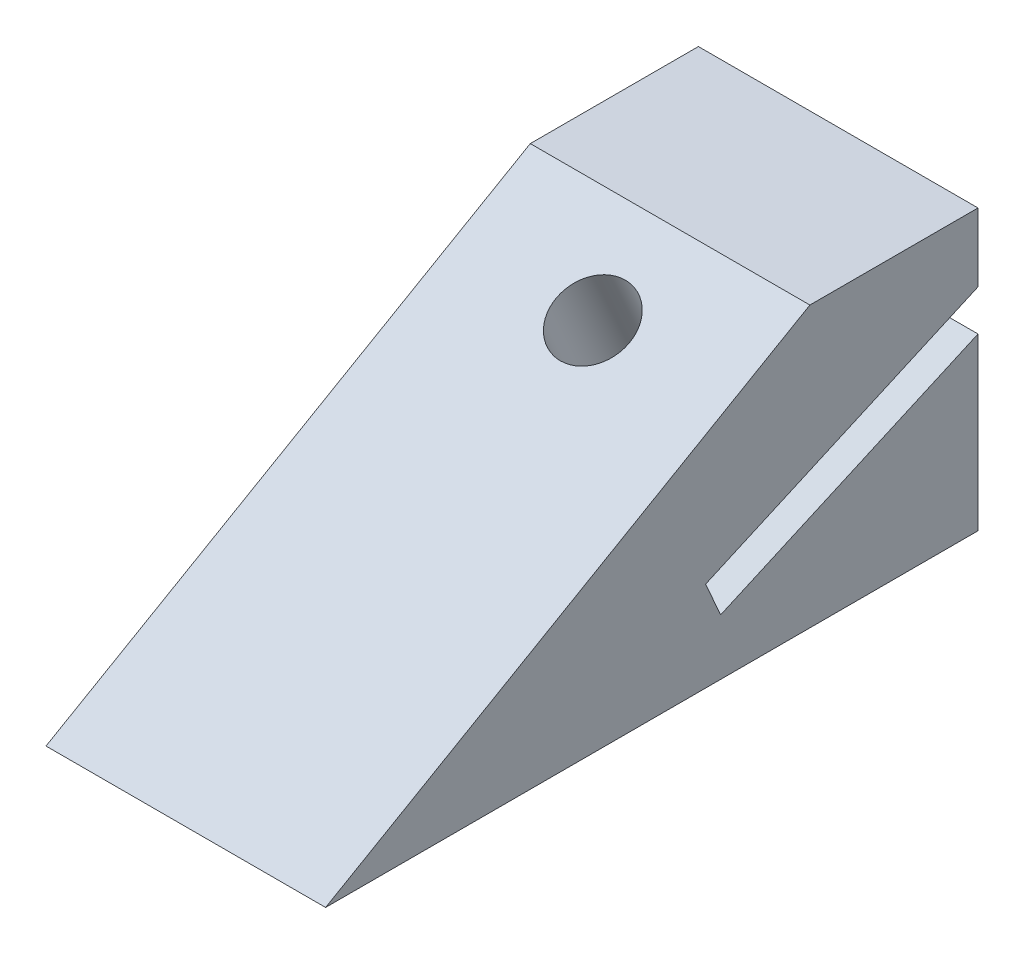
SolidWorks part; units mm, degrees
ref_plane "Front Plane" through (0, 0, 0) normal (0, 0, 1) x (1, 0, 0)
ref_plane "Top Plane" through (0, 0, 0) normal (0, 1, 0) x (1, 0, 0)
ref_plane "Right Plane" through (0, 0, 0) normal (1, 0, 0) x (0, 0, -1)
sketch "Sketch3" plane through (0, 0, 0) normal (1, 0, 0) x (0, 0, -1)
  line L0 (0, 0) -> (25.9808, 15)
  line L1 (35, 15) -> (35, 11.3349)
  line L2 (35, 0) -> (0, 0)
  line L3 (25.9808, 15) -> (35, 15)
  line L9 (20.3833, 4.8271) -> (35, 11.3349)
  line L11 (35, 9.1456) -> (21.1967, 3)
  line L12 (21.1967, 3) -> (20.3833, 4.8271)
  line L13 (35, 9.1456) -> (35, 0)
  point P5 (33.5374, 8.696)
  point P6 (25.38, 14.6532)
  point P10 (0, 0)
  dimension "D1" = 30
  dimension "D2" = 90
  dimension "D3" = 2
  dimension "D4" = 16
  dimension "D5" = 24
  dimension "D6" = 3
  dimension "D7" = 35
  dimension "D8" = 15
extrude "Boss-Extrude2" add sketch "Sketch3" along normal blind 15 contours L0 L1 L3 | L2 L1 region at (0, 5.914, -22.1789)
sketch "Sketch7" plane through (0, -5.3724, -2.392) normal (0, 0.9135, 0.4067) x (1, 0, 0)
  line L0 (7.5, 38.0751) -> (7.5, 22.0751)
  line L1 (15, 38.0751) -> (0, 38.0751) construction
  circle A0 centre (7.5, 25.0751) radius 2
  dimension "D2" = 4
  dimension "D1" = 16
  dimension "D3" = 3
extrude "Cut-Extrude5" cut sketch "Sketch7" along normal blind 11 and the other way blind 2 contours L0 A0 | L0 A0 region at (8.3488, 4.8265, -25.2992) region at (6.6512, 4.8265, -25.2992)
